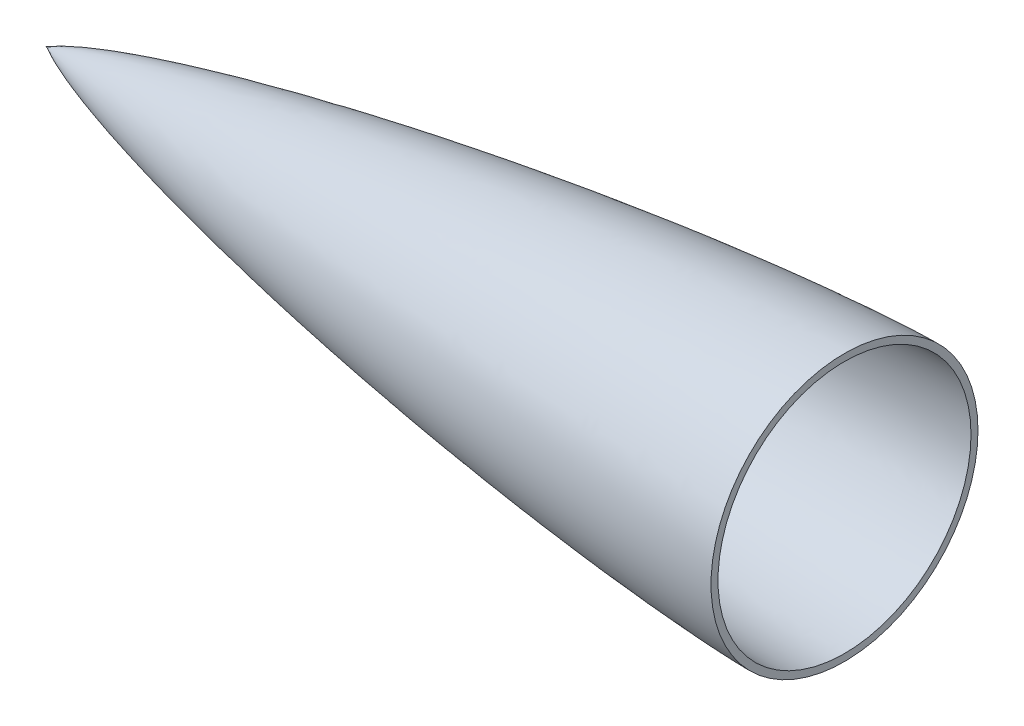
SolidWorks part; units mm, degrees
ref_plane "Front Plane" through (0, 0, 0) normal (0, 0, 1) x (1, 0, 0)
ref_plane "Top Plane" through (0, 0, 0) normal (0, 1, 0) x (1, 0, 0)
ref_plane "Right Plane" through (0, 0, 0) normal (1, 0, 0) x (0, 0, -1)
sketch "Sketch1" plane through (0, 0, 0) normal (0, 1, 0) x (1, 0, 0)
  line L3 (-55, 0) -> (55, 0) construction
  line L4 (200, 33.4356) -> (200, 0)
  line L5 (200, 0) -> (0, 0)
  spline S0 degree 4 poles (0, 0) (0.0297, 0.0027) (0.089, 0.0128) (0.1752, 0.0408) (0.3046, 0.0915) (0.5495, 0.204) (0.9043, 0.3864) (1.5855, 0.7376) (2.7098, 1.2836) (4.4238, 2.0401) (7.065, 3.0857) (10.7984, 4.4109) (16.1615, 6.1222) (23.7399, 8.2919) (33.2254, 10.7239) (44.2444, 13.2746) (56.1293, 15.7818) (68.0528, 18.0982) (80.0071, 20.2486) (91.9875, 22.2489) (103.9905, 24.1086) (116.0136, 25.8328) (128.0552, 27.4233) (140.114, 28.8776) (152.1891, 30.1899) (164.2801, 31.3479) (176.3866, 32.3324) (186.1546, 32.954) (193.5759, 33.2951) (197.9667, 33.411) (199.3222, 33.4323) (200, 33.4356) knots 0 0 0 0 0 0.000585 0.001182 0.001773 0.002733 0.005878 0.009023 0.016834 0.027293 0.042687 0.064838 0.094675 0.13791 0.197585 0.25726 0.316935 0.37661 0.436285 0.495959 0.555634 0.615309 0.674984 0.734659 0.794334 0.854008 0.913683 0.973358 0.986679 1 1 1 1 1 construction
  spline S1 degree 4 poles (0, 0) (0.0297, 0.0027) (0.089, 0.0128) (0.1752, 0.0408) (0.3046, 0.0915) (0.5495, 0.204) (0.9043, 0.3864) (1.5855, 0.7376) (2.7098, 1.2836) (4.4238, 2.0401) (7.065, 3.0857) (10.7984, 4.4109) (16.1615, 6.1222) (23.7399, 8.2919) (33.2254, 10.7239) (44.2444, 13.2746) (56.1293, 15.7818) (68.0528, 18.0982) (80.0071, 20.2486) (91.9875, 22.2489) (103.9905, 24.1086) (116.0136, 25.8328) (128.0552, 27.4233) (140.114, 28.8776) (152.1891, 30.1899) (164.2801, 31.3479) (176.3866, 32.3324) (186.1546, 32.954) (193.5759, 33.2951) (197.9667, 33.411) (199.3222, 33.4323) (200, 33.4356) knots 0 0 0 0 0 0.000585 0.001182 0.001773 0.002733 0.005878 0.009023 0.016834 0.027293 0.042687 0.064838 0.094675 0.13791 0.197585 0.25726 0.316935 0.37661 0.436285 0.495959 0.555634 0.615309 0.674984 0.734659 0.794334 0.854008 0.913683 0.973358 0.986679 1 1 1 1 1
  dimension "D1" = 200
revolve "Revolve1" add sketch "Sketch1" angle 360 about L5
shell "Shell1" thickness 1.75 removed face at (200, 0, -33.4356)
